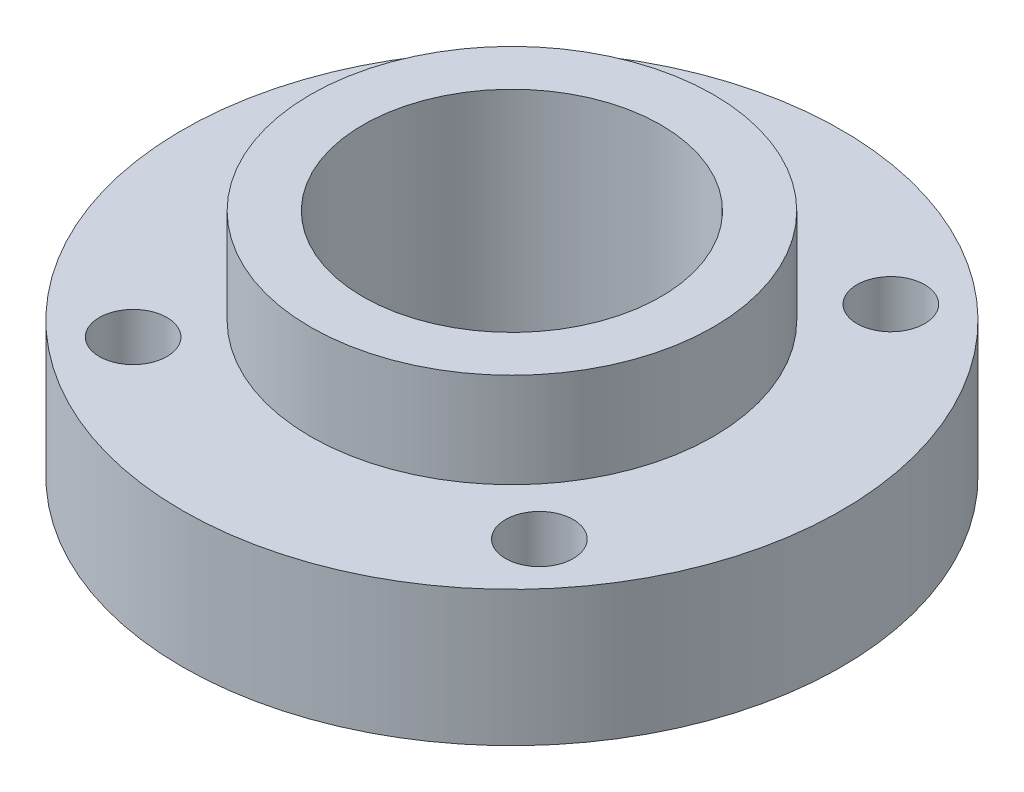
SolidWorks part; units mm, degrees
ref_plane "Front Plane" through (0, 0, 0) normal (0, 0, 1) x (1, 0, 0)
ref_plane "Top Plane" through (0, 0, 0) normal (0, 1, 0) x (1, 0, 0)
ref_plane "Right Plane" through (0, 0, 0) normal (1, 0, 0) x (0, 0, -1)
sketch "Sketch1" plane through (0, 0, 0) normal (0, 1, 0) x (1, 0, 0)
  circle A0 centre (-14.9076, 21.38) radius 24.34
  circle A1 centre (-29.9461, 34.321) radius 2.5
  circle A2 centre (-27.8246, 6.321) radius 2.5
  circle A3 centre (-1.9461, 36.4009) radius 2.5
  circle A4 centre (0.098, 8.4009) radius 2.5
  circle A5 centre (-14.9076, 21.38) radius 14.875
  circle A6 centre (-14.9076, 21.38) radius 7.375
  circle A7 centre (-14.9076, 21.38) radius 11
  dimension "D1" = 48.68
  dimension "D2" = 5
  dimension "D4" = 19.84
  dimension "D6" = 29.75
  dimension "D7" = 28
  dimension "D8" = 14.75
  dimension "D9" = 28
  dimension "D13" = 22
  dimension "D3" = 28
  dimension "D5" = 28
  dimension "D10" = 19.84
  dimension "D11" = 19.84
  dimension "D12" = 19.84
extrude "Boss-Extrude13" add sketch "Sketch1" along normal blind 17 contours A5 A6 region at (-29.3618, 0, -21.38)
extrude "Boss-Extrude14" add sketch "Sketch1<14>" along normal blind 10 contours A0 A5 A4 A3 A2 A1 region at (-38.5591, 0, -21.38)
sketch "Sketch1<14>" plane through (0, 0, 0) normal (0, 1, 0) x (1, 0, 0) same geometry as "Sketch1"
extrude "Boss-Extrude15" add sketch "Sketch1<16>" along normal blind 1 contours A7 A6 region at (-25.5964, 0, -21.38)
sketch "Sketch1<16>" plane through (0, 0, 0) normal (0, 1, 0) x (1, 0, 0) same geometry as "Sketch1"
